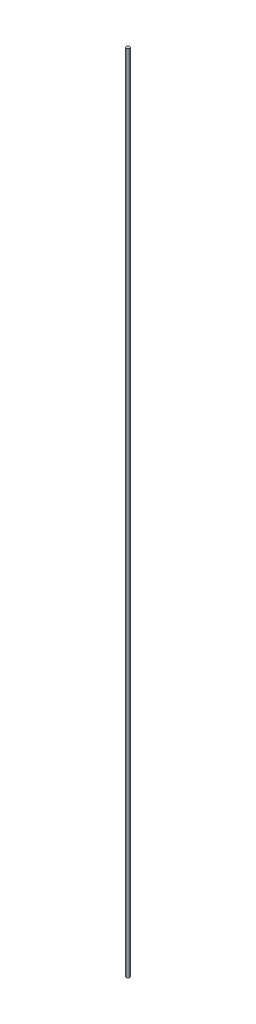
SolidWorks part; units mm, degrees
ref_plane "Front Plane" through (0, 0, 0) normal (0, 0, 1) x (1, 0, 0)
ref_plane "Top Plane" through (0, 0, 0) normal (0, 1, 0) x (1, 0, 0)
ref_plane "Right Plane" through (0, 0, 0) normal (1, 0, 0) x (0, 0, -1)
sketch "Sketch1" plane through (0, 0, 0) normal (0, 1, 0) x (1, 0, 0)
  circle A0 centre (0, 0) radius 0.635
  dimension "D1" = 1.27
extrude "Boss-Extrude1" add sketch "Sketch1" along normal blind 304.8
ref_axis "Axis1" through (0, 304.8, 0) along (0, -1, 0)
ref_point "Point1"
